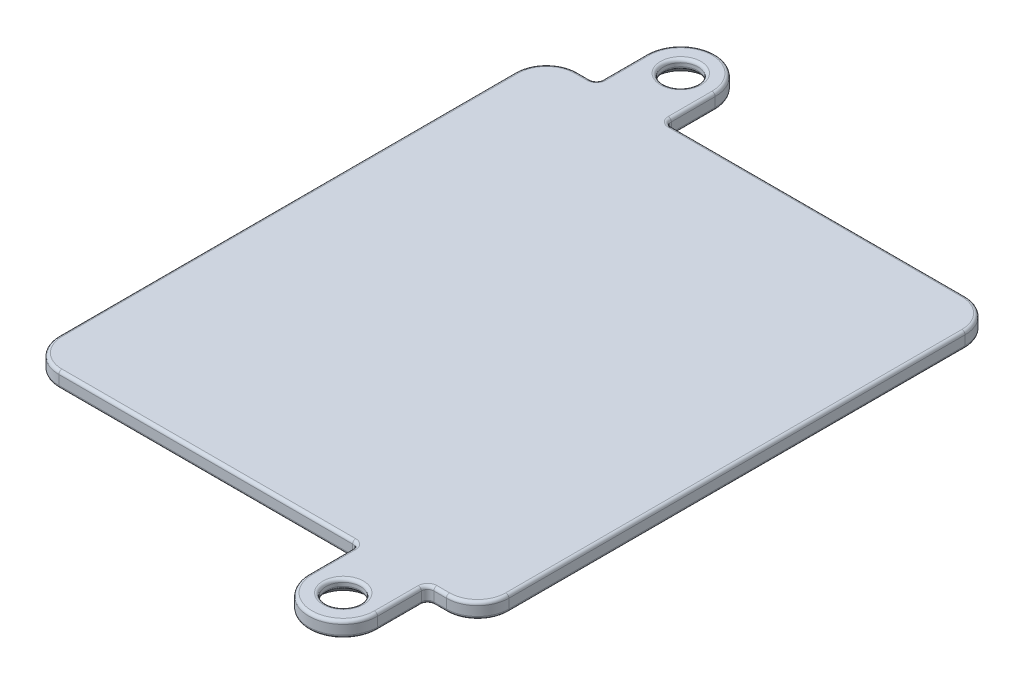
SolidWorks part; units mm, degrees
ref_plane "Front Plane" through (0, 0, 0) normal (0, 0, 1) x (1, 0, 0)
ref_plane "Top Plane" through (0, 0, 0) normal (0, 1, 0) x (1, 0, 0)
ref_plane "Right Plane" through (0, 0, 0) normal (1, 0, 0) x (0, 0, -1)
sketch "Sketch1" plane through (0, 0, 0) normal (0, 1, 0) x (1, 0, 0)
  line L10 (36, -36.5) -> (36, 36.5)
  line L11 (-29, 41.5) -> (-31, 41.5)
  line L12 (-28, 42.5) -> (-28, 49.5)
  line L13 (-17, 49.5) -> (-17, 42.5)
  line L14 (31, 41.5) -> (-16, 41.5)
  line L15 (29, -41.5) -> (31, -41.5)
  line L16 (28, -42.5) -> (28, -49.5)
  line L17 (17, -49.5) -> (17, -42.5)
  line L18 (-31, -41.5) -> (16, -41.5)
  line L19 (-36, 36.5) -> (-36, -36.5)
  line L20 (-67.6496, 0) -> (67.5062, 0) construction
  line L21 (0, 60.4472) -> (0, -62.9116) construction
  arc A10 (31, -41.5) -> (36, -36.5) centre (31, -36.5) ccw
  arc A11 (36, 36.5) -> (31, 41.5) centre (31, 36.5) ccw
  arc A12 (-31, 41.5) -> (-36, 36.5) centre (-31, 36.5) ccw
  arc A13 (-29, 41.5) -> (-28, 42.5) centre (-29, 42.5) ccw
  arc A14 (-17, 49.5) -> (-28, 49.5) centre (-22.5, 49.5) ccw
  arc A15 (-17, 42.5) -> (-16, 41.5) centre (-16, 42.5) ccw
  arc A16 (29, -41.5) -> (28, -42.5) centre (29, -42.5) ccw
  arc A17 (17, -49.5) -> (28, -49.5) centre (22.5, -49.5) ccw
  arc A18 (17, -42.5) -> (16, -41.5) centre (16, -42.5) ccw
  arc A19 (-36, -36.5) -> (-31, -41.5) centre (-31, -36.5) ccw
  dimension "D3" = 5
  dimension "D4" = 5
  dimension "D5" = 5
  dimension "D6" = 5
  dimension "D11" = 5.5
  dimension "D12" = 5.5
  dimension "D13" = 1
  dimension "D14" = 1
  dimension "D15" = 1
  dimension "D16" = 1
  dimension "D1" = 72
  dimension "D2" = 83
  dimension "D7" = 22.5
  dimension "D8" = 22.5
  dimension "D9" = 8
  dimension "D10" = 8
extrude "Boss-Extrude1" add sketch "Sketch1" along normal blind 1.25 and the other way blind 1.25
sketch "Sketch2" plane through (0, 1.25, 0) normal (0, 1, 0) x (1, 0, 0)
  circle A0 centre (22.5, -49.5) radius 2.75
  circle A1 centre (-22.5, 49.5) radius 2.75
  arc A2 (17, -49.5) -> (28, -49.5) centre (22.5, -49.5) ccw construction
  arc A3 (-17, 49.5) -> (-28, 49.5) centre (-22.5, 49.5) ccw construction
  dimension "D1" = 5.5
  dimension "D2" = 5.5
extrude "Cut-Extrude1" cut sketch "Sketch2" against normal up to next
chamfer "Chamfer1" distance 1.25 angle 45 2 edges at (22.5, -1.25, 52.25) (-22.5, -1.25, -46.75)
fillet "Fillet1" radius 0.5 44 edges at (-34.5355, -1.25, -40.0355) (-30, -1.25, -41.5) (-28.2929, -1.25, -41.7929) (-28, -1.25, -46) (-22.5, -1.25, -55) (-17, -1.25, -46) (-16.7071, -1.25, -41.7929) (7.5, -1.25, -41.5) (34.5355, -1.25, -40.0355) (36, -1.25, 0) (34.5355, -1.25, 40.0355) (30, -1.25, 41.5) (28.2929, -1.25, 41.7929) (28, -1.25, 46) (22.5, -1.25, 55) (17, -1.25, 46) (16.7071, -1.25, 41.7929) (-7.5, -1.25, 41.5) (-34.5355, -1.25, 40.0355) (-34.5355, 1.25, -40.0355) (-30, 1.25, -41.5) (-28.2929, 1.25, -41.7929) (-28, 1.25, -46) (-22.5, 1.25, -55) (-17, 1.25, -46) (-16.7071, 1.25, -41.7929) (7.5, 1.25, -41.5) (34.5355, 1.25, -40.0355) (36, 1.25, 0) (34.5355, 1.25, 40.0355) (30, 1.25, 41.5) (28.2929, 1.25, 41.7929) (28, 1.25, 46) (22.5, 1.25, 55) (17, 1.25, 46) (16.7071, 1.25, 41.7929) (-7.5, 1.25, 41.5) (-34.5355, 1.25, 40.0355) (-36, -1.25, 0) (-36, 1.25, 0) (22.5, 1.25, 52.25) (22.5, 0, 52.25) (-22.5, 1.25, -46.75) (-22.5, 0, -46.75)
